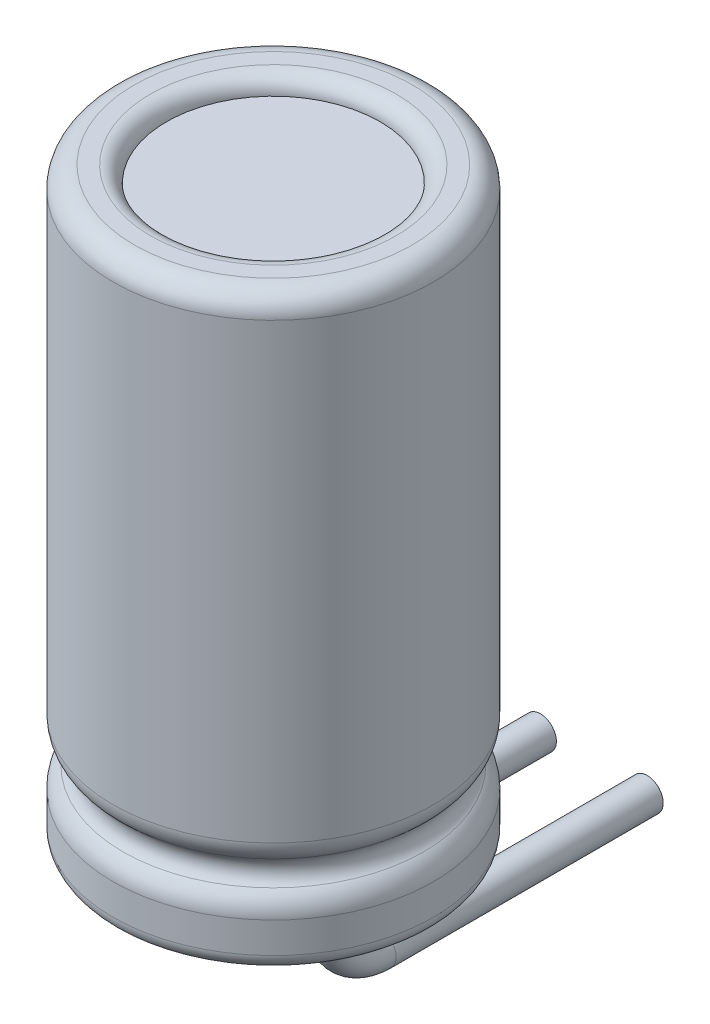
SolidWorks part; units mm, degrees
ref_plane "Front Plane" through (0, 0, 0) normal (0, 0, 1) x (1, 0, 0)
ref_plane "Top Plane" through (0, 0, 0) normal (0, 1, 0) x (1, 0, 0)
ref_plane "Right Plane" through (0, 0, 0) normal (1, 0, 0) x (0, 0, -1)
sketch "Эскиз2" plane through (0, 0, 0) normal (0, 1, 0) x (1, 0, 0)
  circle A0 centre (0, 0) radius 3
  dimension "D1" = 6
extrude "Бобышка-Вытянуть1" add sketch "Эскиз2" along normal blind 11
sketch "Эскиз3" plane through (0, 0, 0) normal (0, -1, 0) x (1, 0, 0)
  circle A0 centre (0, 0) radius 2
  dimension "D1" = 4
extrude "Вырез-Вытянуть1" cut sketch "Эскиз3" against normal blind 0.3
sketch "Эскиз4" plane through (0, 0.3, 0) normal (0, -1, 0) x (1, 0, 0)
  line L0 (0, 3.1513) -> (0, -3.4223) construction
  line L1 (-3.3944, 0) -> (3.3545, 0) construction
  circle A0 centre (-1, 0) radius 0.3
  dimension "D1" = 0.6
  dimension "D2" = 1
ref_plane "Плоскость1" through (-1, 0, 0) normal (-1, 0, 0) x (0, 0, 1)
sketch "Эскиз6" plane through (-1, 0, 0) normal (-1, 0, 0) x (0, 0, 1)
  line L0 (0, 0.3) -> (0, -0.7)
  line L1 (-0.3, 0.3) -> (0.3, 0.3) construction
  line L2 (-1, -1.7) -> (-6, -1.7)
  arc A0 (-1, -1.7) -> (0, -0.7) centre (-1, -0.7) ccw
  point P8 (0, -1.7)
  dimension "D3" = 1
  dimension "D1" = 2
  dimension "D2" = 6
sweep "По траектории1" add profiles "Эскиз4" path "Эскиз6"
mirror "Зеркальное отражение1" about plane through (0, 0, 0) normal (1, 0, 0) of bodies 103
sketch "Эскиз7" plane through (0, 11, 0) normal (0, 1, 0) x (1, 0, 0)
  circle A0 centre (0, 0) radius 2
  dimension "D1" = 4
extrude "Вырез-Вытянуть2" cut sketch "Эскиз7" against normal blind 0.3
sketch "Эскиз9" plane through (0, 0, 0) normal (1, 0, 0) x (0, 0, -1)
  line L0 (-3, 11) -> (-3, 0) construction
  line L1 (-3, 11) -> (-3, 0) construction
  line L2 (-3, 11) -> (-3, 0) construction
  line L3 (0, -2.3692) -> (0, 14.89) construction
  line L4 (-3, 1.8) -> (-3, 1.2)
  arc A0 (-3, 1.8) -> (-3, 1.2) centre (-3, 1.5) cw
  dimension "D2" = 0.3
  dimension "D1" = 1.5
revolve "Вырез-Повернуть1" cut sketch "Эскиз9" angle 360 about L3
fillet "Скругление2" radius 0.5 2 edges at (0, 1.8, -3) (0, 1.2, -3)
fillet "Скругление3" radius 0.4 1 edges at (0, 11, 3)
fillet "Скругление4" radius 0.3 1 edges at (0, 11, 2)
fillet "Скругление5" radius 0.3 1 edges at (0, 0, -2)
fillet "Скругление6" radius 0.3 1 edges at (0, 0, 3)
